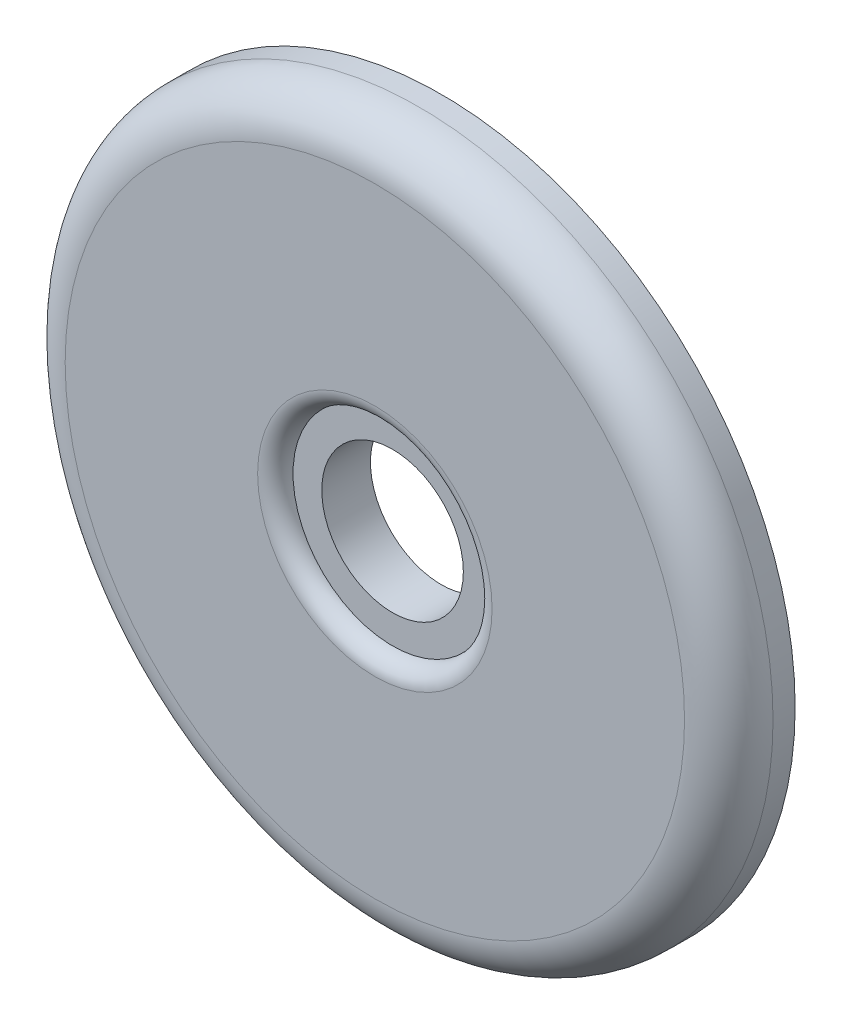
SolidWorks part; units mm, degrees
ref_plane "Спереди" through (0, 0, 0) normal (0, 0, 1) x (1, 0, 0)
ref_plane "Сверху" through (0, 0, 0) normal (0, 1, 0) x (1, 0, 0)
ref_plane "Справа" through (0, 0, 0) normal (1, 0, 0) x (0, 0, -1)
sketch "Эскиз1" plane through (0, 0, 0) normal (0, 0, 1) x (1, 0, 0)
  circle A0 centre (0, 0) radius 8
  circle A1 centre (0, 0) radius 1.6
  dimension "D1" = 16
  dimension "D2" = 3.2
extrude "Бобышка-Вытянуть1" add sketch "Эскиз1" along normal blind 1.5
fillet "Скругление1" radius 1 1 edges at (8, 0, 1.5)
sketch "Эскиз3" plane through (0, 0, 1.5) normal (0, 0, 1) x (1, 0, 0)
  circle A0 centre (0, 0) radius 2.25
  dimension "D1" = 4.5
extrude "Вырез-Вытянуть3" cut sketch "Эскиз3" against normal blind 0.4
fillet "Скругление2" radius 0.4 1 edges at (2.25, 0, 1.5)
